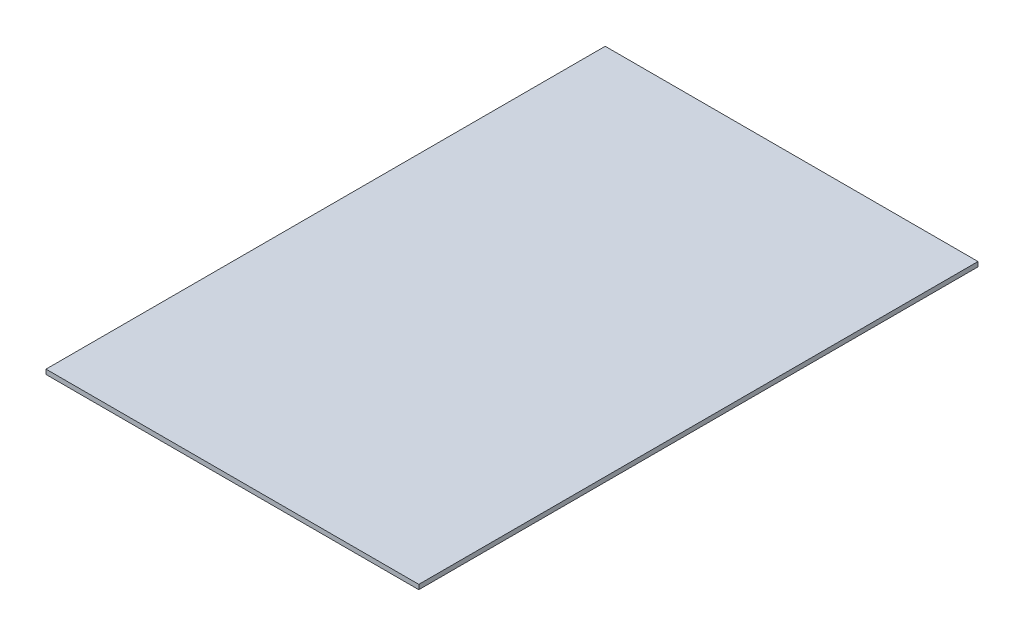
SolidWorks part; units mm, degrees
ref_plane "Ebene vorne" through (0, 0, 0) normal (0, 0, 1) x (1, 0, 0)
ref_plane "Ebene oben" through (0, 0, 0) normal (0, 1, 0) x (1, 0, 0)
ref_plane "Ebene rechts" through (0, 0, 0) normal (1, 0, 0) x (0, 0, -1)
sketch "Skizze2" plane through (0, 0, 0) normal (0, 1, 0) x (1, 0, 0)
  line L1 (400, 600) -> (-400, 600)
  line L2 (400, 600) -> (400, -600)
  line L3 (400, -600) -> (-400, -600)
  line L4 (-400, 600) -> (-400, -600)
  line L5 (400, 600) -> (-400, -600) construction
  line L6 (400, -600) -> (-400, 600) construction
  point P0 (0, 0)
  point P6 (0, 0)
  dimension "D1" = 1200
  dimension "D2" = 800
extrude "Aufsatz-Linear austragen1" add sketch "Skizze2" along normal blind 10
ref_point "Punkt1"
ref_plane "Ebene1" through (0, 10, 0) normal (0, 0, -1) x (-1, 0, 0)
ref_plane "Ebene2" through (0, 10, 0) normal (1, 0, 0) x (0, 0, -1)
ref_axis "Achse1" through (0, -210, 0) along (0, 1, 0)
